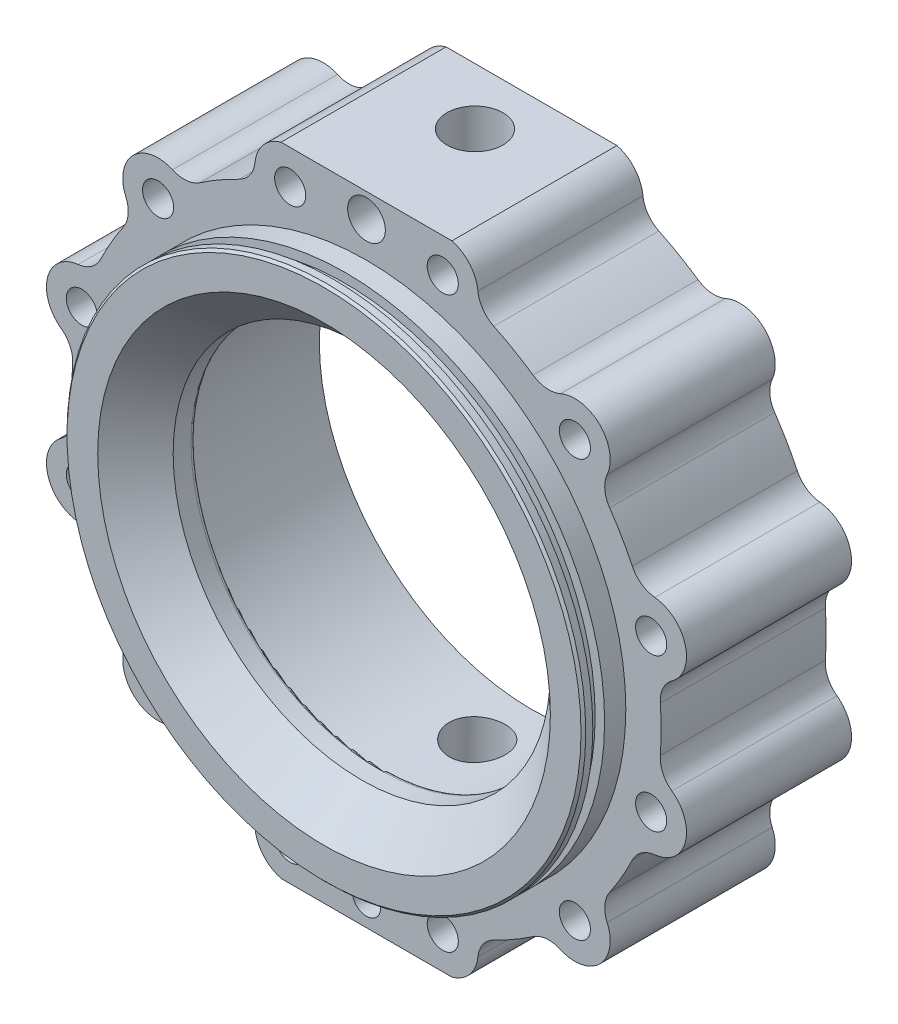
SolidWorks part; units mm, degrees
ref_plane "Front Plane" through (0, 0, 0) normal (0, 0, 1) x (1, 0, 0)
ref_plane "Top Plane" through (0, 0, 0) normal (0, 1, 0) x (1, 0, 0)
ref_plane "Right Plane" through (0, 0, 0) normal (1, 0, 0) x (0, 0, -1)
sketch "Sketch1" plane through (0, 0, 0) normal (0, 1, 0) x (1, 0, 0)
  line L0 (-55, -18.7958) -> (-55, -9.7958)
  line L2 (-55, -9.7958) -> (-70, -9.7958)
  line L3 (-55, -18.7958) -> (-40, -18.7958)
  line L4 (-40, -18.7958) -> (-40, -6)
  line L5 (-40, -6) -> (-45, -6)
  line L6 (-45, -6) -> (-45, 25.2042)
  line L7 (-45, 25.2042) -> (-70, 25.2042)
  line L8 (-70, 25.2042) -> (-70, -9.7958)
  line L12 (0, 52.7074) -> (0, -119.6493) construction
  dimension "D1" = 80
  dimension "D2" = 31.2042
  dimension "D3" = 140
  dimension "D4" = 90
  dimension "D5" = 110
  dimension "D6" = 9
revolve "Revolve1" add sketch "Sketch1" angle 360 about L12
sketch "Sketch2" plane through (0, 0, 9.7958) normal (0, 0, 1) x (1, 0, 0)
  line L0 (0, 62.5) -> (0, -62.5) construction
  circle A0 centre (0, 0) radius 62.5 construction
  circle A2 centre (0, -62.5) radius 3
  dimension "D1" = 125
  dimension "D3" = 6
extrude "Cut-Extrude1" cut sketch "Sketch2" against normal blind 9 contours A2
sketch "Sketch3" plane through (0, 0, 9.7958) normal (0, 0, 1) x (1, 0, 0)
  line L0 (0, 0) -> (0, 62.5) construction
  circle A0 centre (0, 62.5) radius 4
  dimension "D2" = 8
  dimension "D1" = 62.5
extrude "Cut-Extrude2" cut sketch "Sketch3" against normal blind 10
sketch "Bolt Holes" plane through (0, 0, 9.7958) normal (0, 0, 1) x (1, 0, 0)
  line L2 (-44.1942, 44.1942) -> (0, 0) construction
  line L3 (0, 0) -> (0, 62.5) construction
  circle A1 centre (0, 0) radius 62.5 construction
  point P0 (-60.3704, 16.1762)
  point P5 (-44.1942, 44.1942)
  point P8 (-16.1762, 60.3704)
  point P11 (16.1762, 60.3704)
  point P15 (44.1942, 44.1942)
  point P16 (60.3704, 16.1762)
  point P17 (60.3704, -16.1762)
  point P18 (44.1942, -44.1942)
  point P19 (16.1762, -60.3704)
  point P20 (-16.1762, -60.3704)
  point P21 (-44.1942, -44.1942)
  point P22 (-60.3704, -16.1762)
  point P23 (0, 0)
  point P30 (-44.1942, 44.1942)
  point P37 (44.1942, -44.1942)
  dimension "D3" = 45
  dimension "D2" = 125
  dimension "D1" = 12
sketch "Sketch9" plane through (0, 0, 0) normal (0, 1, 0) x (1, 0, 0)
  line L0 (-55, -9.7958) -> (-55, -18.7958) construction
  line L1 (-55, -16.7958) -> (-53, -16.7958)
  line L2 (-55, -16.7958) -> (-55, -14.2958)
  line L3 (-55, -14.2958) -> (-53, -14.2958)
  line L4 (-53, -16.7958) -> (-53, -14.2958)
  line L6 (0, 11.3077) -> (0, -18.9957) construction
  dimension "D1" = 2
  dimension "50" = 53
  dimension "D2" = 2.5
revolve "Oring groove" cut sketch "Sketch9" angle 360 about L6
chamfer "Chamfer1" distance 0.5 angle 45 1 edges at (-55, 0, 18.7958)
hole_wizard "M6 Clearance Hole1" positions "Bolt Holes" profile "Sketch10" hole size "M6" standard "ANSI Metric" end condition through all
sketch "Sketch10" plane through (-60.3704, 16.1762, 9.7958) normal (1, 0, 0) x (0, -1, 0)
  line L0 (0, 0) -> (0, 35)
  line L1 (0, 35) -> (3.3, 35)
  line L2 (3.3, 35) -> (3.3, 0)
  line L5 (3.3, 0) -> (0, 0)
  line L11 (0, -6.35) -> (0, 107.95) construction
  dimension "Thru Hole Dia." = 6.6
  dimension "Thru Hole Depth" = 35
fillet "Fillet2" radius 1 1 edges at (-40, 0, 6)
chamfer "Chamfer2" distance 8 angle 45 1 edges at (-40, 0, 18.7958)
sketch "Sketch11" plane through (0, 0, -25.2042) normal (0, 0, -1) x (-1, 0, 0)
  line L0 (-18.1173, 67.6148) -> (18.1173, 67.6148)
  line L1 (-18.1173, -67.6148) -> (18.1173, -67.6148)
  arc A0 (-64.7749, -10.1058) -> (-61.1496, -23.6356) centre (-60.3704, -16.1762) ccw
  arc A1 (-56.3622, -27.0102) -> (-61.1496, -23.6356) centre (-61.773, -29.6031) ccw
  arc A2 (-56.3622, -27.0102) -> (-51.5726, -35.3061) centre (0, 0) ccw
  arc A3 (-51.0438, -41.1393) -> (-51.5726, -35.3061) centre (-56.5236, -38.6954) ccw
  arc A4 (-51.0438, -41.1393) -> (-41.1393, -51.0438) centre (-44.1942, -44.1942) ccw
  arc A5 (-35.3061, -51.5726) -> (-41.1393, -51.0438) centre (-38.6954, -56.5236) ccw
  arc A6 (-35.3061, -51.5726) -> (-27.0102, -56.3622) centre (0, 0) ccw
  arc A7 (-23.6356, -61.1496) -> (-27.0102, -56.3622) centre (-29.6031, -61.773) ccw
  arc A8 (-23.6356, -61.1496) -> (-18.1173, -67.6148) centre (-16.1762, -60.3704) ccw
  arc A10 (18.1173, -67.6148) -> (23.6356, -61.1496) centre (16.1762, -60.3704) ccw
  arc A11 (27.0102, -56.3622) -> (23.6356, -61.1496) centre (29.6031, -61.773) ccw
  arc A12 (27.0102, -56.3622) -> (35.3061, -51.5726) centre (0, 0) ccw
  arc A13 (41.1393, -51.0438) -> (35.3061, -51.5726) centre (38.6954, -56.5236) ccw
  arc A14 (41.1393, -51.0438) -> (51.0438, -41.1393) centre (44.1942, -44.1942) ccw
  arc A15 (51.5726, -35.3061) -> (51.0438, -41.1393) centre (56.5236, -38.6954) ccw
  arc A16 (51.5726, -35.3061) -> (56.3622, -27.0102) centre (0, 0) ccw
  arc A17 (61.1496, -23.6356) -> (56.3622, -27.0102) centre (61.773, -29.6031) ccw
  arc A18 (61.1496, -23.6356) -> (64.7749, -10.1058) centre (60.3704, -16.1762) ccw
  arc A19 (62.3162, -4.7896) -> (64.7749, -10.1058) centre (68.2986, -5.2494) ccw
  arc A20 (62.3162, -4.7896) -> (62.3162, 4.7896) centre (0, 0) ccw
  arc A21 (64.7749, 10.1058) -> (62.3162, 4.7896) centre (68.2986, 5.2494) ccw
  arc A22 (64.7749, 10.1058) -> (61.1496, 23.6356) centre (60.3704, 16.1762) ccw
  arc A23 (56.3622, 27.0102) -> (61.1496, 23.6356) centre (61.773, 29.6031) ccw
  arc A24 (56.3622, 27.0102) -> (51.5726, 35.3061) centre (0, 0) ccw
  arc A25 (51.0438, 41.1393) -> (51.5726, 35.3061) centre (56.5236, 38.6954) ccw
  arc A26 (51.0438, 41.1393) -> (41.1393, 51.0438) centre (44.1942, 44.1942) ccw
  arc A27 (35.3061, 51.5726) -> (41.1393, 51.0438) centre (38.6954, 56.5236) ccw
  arc A28 (35.3061, 51.5726) -> (27.0102, 56.3622) centre (0, 0) ccw
  arc A29 (23.6356, 61.1496) -> (27.0102, 56.3622) centre (29.6031, 61.773) ccw
  arc A30 (23.6356, 61.1496) -> (18.1173, 67.6148) centre (16.1762, 60.3704) ccw
  arc A32 (-18.1173, 67.6148) -> (-23.6356, 61.1496) centre (-16.1762, 60.3704) ccw
  arc A33 (-27.0102, 56.3622) -> (-23.6356, 61.1496) centre (-29.6031, 61.773) ccw
  arc A34 (-27.0102, 56.3622) -> (-35.3061, 51.5726) centre (0, 0) ccw
  arc A35 (-41.1393, 51.0438) -> (-35.3061, 51.5726) centre (-38.6954, 56.5236) ccw
  arc A36 (-41.1393, 51.0438) -> (-51.0438, 41.1393) centre (-44.1942, 44.1942) ccw
  arc A37 (-51.5726, 35.3061) -> (-51.0438, 41.1393) centre (-56.5236, 38.6954) ccw
  arc A38 (-51.5726, 35.3061) -> (-56.3622, 27.0102) centre (0, 0) ccw
  arc A39 (-61.1496, 23.6356) -> (-56.3622, 27.0102) centre (-61.773, 29.6031) ccw
  arc A40 (-61.1496, 23.6356) -> (-64.7749, 10.1058) centre (-60.3704, 16.1762) ccw
  arc A41 (-62.3162, 4.7896) -> (-64.7749, 10.1058) centre (-68.2986, 5.2494) ccw
  arc A42 (-62.3162, 4.7896) -> (-62.3162, -4.7896) centre (0, 0) ccw
  arc A43 (-64.7749, -10.1058) -> (-62.3162, -4.7896) centre (-68.2986, -5.2494) ccw
  circle A44 centre (0, 0) radius 70 construction
  arc A45 (-18.1173, 67.6148) -> (-18.1173, -67.6148) centre (0, 0) ccw
  arc A46 (18.1173, -67.6148) -> (18.1173, 67.6148) centre (0, 0) ccw
  circle A47 centre (16.1762, -60.3704) radius 3.3 construction
  circle A48 centre (-44.1942, -44.1942) radius 3.3 construction
  circle A49 centre (-60.3704, -16.1762) radius 3.3 construction
  circle A50 centre (-60.3704, 16.1762) radius 3.3 construction
  circle M57 centre (0, 0) radius 70
  dimension "D1" = 7.5
  dimension "D2" = 6
extrude "looksmaxxing" cut sketch "Sketch11" against normal through all contours A30 A29 A28 A27 A26 M57 | A26 A25 A24 A23 A22 M57 | A22 A21 A20 A19 A18 M57 | A18 A17 A16 A15 A14 M57 | A14 A13 A12 A11 A10 M57 | A8 A7 A6 A5 A4 M57 | A4 A3 A2 A1 A0 M57 | A0 A43 A42 A41 A40 M57 | A40 A39 A38 A37 A36 M57 | A36 A35 A34 A33 A32 M57 | L0 M57 | L1 M57 region at (0, 68.5703, -25.2042) region at (33.2057, 57.514, -25.2042) region at (-33.2057, 57.514, -25.2042) region at (57.514, 33.2057, -25.2042) region at (-57.514, 33.2057, -25.2042) region at (66.4115, 0, -25.2042) region at (-66.4115, 0, -25.2042) region at (57.514, -33.2057, -25.2042) region at (33.2057, -57.514, -25.2042) region at (-57.514, -33.2057, -25.2042) region at (0, -68.5703, -25.2042) region at (-33.2057, -57.514, -25.2042)
hole_wizard "1/4-18 NPSM Tapped Hole1" positions "Sketch13" profile "Sketch14" tap size "1/4-18 NPSM" standard "ANSI Inch"
sketch "Sketch13" plane through (0, 67.6148, 0) normal (0, 1, 0) x (1, 0, 0)
  line L0 (0, 0) -> (0, 25.2042) construction
  line L1 (18.1173, 25.2042) -> (-18.1173, 25.2042) construction
  point P8 (0, 13.2042)
  dimension "D1" = 12
sketch "Sketch14" plane through (0, 67.6148, -13.2042) normal (1, 0, 0) x (0, 0, 1)
  line L0 (0, 0) -> (0, 34.5313)
  line L1 (0, 34.5313) -> (5.9436, 30.96)
  line L2 (5.9436, 30.96) -> (5.9436, 0)
  line L5 (5.9436, 0) -> (0, 0)
  line L10 (0, 34.5313) -> (-5.9436, 30.96) construction
  line L11 (0, -6.35) -> (0, 107.95) construction
  dimension "Tap Drill Dia." = 11.8872
  dimension "Tap Drill Depth" = 30.96
  dimension "Drill Angle" = 118
cosmetic thread "Hole Thread1" parameters "D1"=26.72, "D2"=13.3604
hole_wizard "1/4-18 NPSM Tapped Hole2" positions "Sketch15" profile "Sketch16" tap size "1/4-18 NPSM" standard "ANSI Inch"
sketch "Sketch15" plane through (0, -67.6148, 0) normal (0, -1, 0) x (1, 0, 0)
  line L0 (18.1173, -25.2042) -> (-18.1173, -25.2042) construction
  point P0 (0, -13.7042)
  dimension "D1" = 11.5
sketch "Sketch16" plane through (0, -67.6148, -13.7042) normal (1, 0, 0) x (0, 0, -1)
  line L0 (0, 0) -> (0, 34.5313)
  line L1 (0, 34.5313) -> (5.9436, 30.96)
  line L2 (5.9436, 30.96) -> (5.9436, 0)
  line L5 (5.9436, 0) -> (0, 0)
  line L10 (0, 34.5313) -> (-5.9436, 30.96) construction
  line L11 (0, -6.35) -> (0, 107.95) construction
  dimension "Tap Drill Dia." = 11.8872
  dimension "Tap Drill Depth" = 30.96
  dimension "Drill Angle" = 118
cosmetic thread "Hole Thread2" parameters "D1"=26.72, "D2"=13.3604
